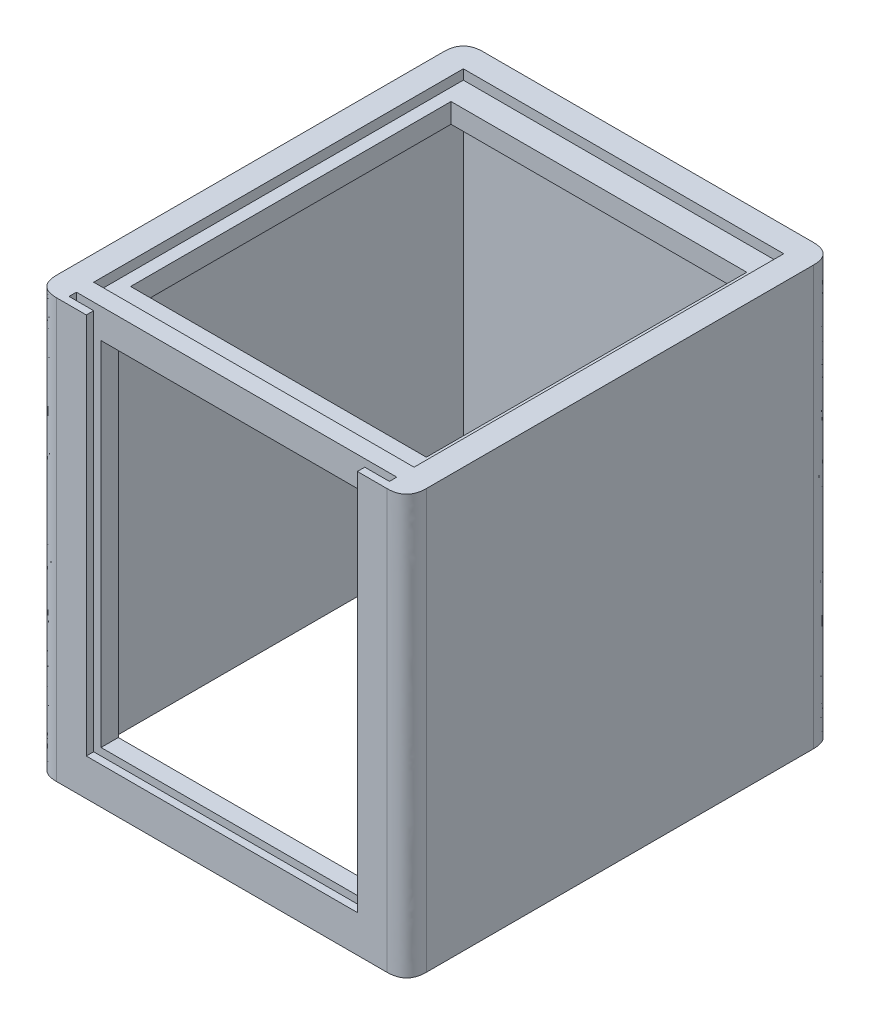
SolidWorks part; units mm, degrees
ref_plane "前基準面" through (0, 0, 0) normal (0, 0, 1) x (1, 0, 0)
ref_plane "上基準面" through (0, 0, 0) normal (0, 1, 0) x (1, 0, 0)
ref_plane "右基準面" through (0, 0, 0) normal (1, 0, 0) x (0, 0, -1)
sketch "草圖2" plane through (0, 0, 0) normal (0, 1, 0) x (1, 0, 0)
  line L1 (-75, -85) -> (75, -85)
  line L2 (-75, -85) -> (-75, 85)
  line L3 (-75, 85) -> (75, 85)
  line L4 (75, -85) -> (75, 85)
  line L5 (-75, -85) -> (75, 85) construction
  line L6 (-75, 85) -> (75, -85) construction
  point P0 (0, 0)
  dimension "D1" = 150
  dimension "D2" = 170
extrude "填料-伸長2" add sketch "草圖2" along normal blind 170
shell "薄殼5" thickness 4 removed face at (0, 0, 0) removed face at (0, 85, 85)
sketch "草圖3" plane through (0, 170, 0) normal (0, 1, 0) x (1, 0, 0)
  line L1 (-65, -75) -> (65, -75)
  line L2 (-65, -75) -> (-65, 75)
  line L3 (-65, 75) -> (65, 75)
  line L4 (65, -75) -> (65, 75)
  line L5 (-65, -75) -> (65, 75) construction
  line L6 (-65, 75) -> (65, -75) construction
  point P0 (0, 0)
  dimension "D1" = 150
  dimension "D2" = 130
extrude "除料-伸長1" cut sketch "草圖3" against normal through all
sketch "草圖4" plane through (0, 166, 0) normal (0, -1, 0) x (1, 0, 0)
  line L1 (60, -65) -> (-60, -65)
  line L2 (60, -65) -> (60, 65)
  line L3 (60, 65) -> (-60, 65)
  line L4 (-60, -65) -> (-60, 65)
  line L5 (60, -65) -> (-60, 65) construction
  line L6 (60, 65) -> (-60, -65) construction
  line L7 (75, -85) -> (-75, -85)
  line L8 (75, -85) -> (75, 85)
  line L9 (75, 85) -> (-75, 85)
  line L10 (-75, -85) -> (-75, 85)
  line L11 (75, -85) -> (-75, 85) construction
  line L12 (75, 85) -> (-75, -85) construction
  point P0 (0, 0)
  point P6 (0, 0)
  dimension "D1" = 120
  dimension "D2" = 130
extrude "填料-伸長3" add sketch "草圖4" along normal blind 8
sketch "草圖5" plane through (0, 0, 85) normal (0, 0, 1) x (1, 0, 0)
  line L0 (55, 170) -> (75, 170)
  line L1 (-75, 170) -> (-55, 170)
  line L2 (-75, 170) -> (-75, 0)
  line L3 (-75, 0) -> (75, 0)
  line L4 (75, 170) -> (75, 0)
  line L6 (-55, 170) -> (-55, 15)
  line L7 (-55, 15) -> (55, 15)
  line L8 (55, 170) -> (55, 15)
  dimension "D1" = 20
  dimension "D2" = 20
  dimension "D3" = 15
extrude "填料-伸長4" add sketch "草圖5" against normal up to surface (10 mm away) and the other way blind 3 up to face at (0, 168, 75)
sketch "草圖6" plane through (0, 170, 0) normal (0, 1, 0) x (1, 0, 0)
  line L0 (-55, -85) -> (55, -85) construction
  line L1 (-65, -85) -> (65, -85)
  line L2 (-65, -85) -> (-65, -82)
  line L3 (-65, -82) -> (65, -82)
  line L4 (65, -85) -> (65, -82)
  line L5 (0, -82) -> (0, 0) construction
  dimension "D1" = 130
  dimension "D2" = 3
extrude "除料-伸長2" cut sketch "草圖6" against normal blind 165
fillet "圓角1" radius 8 4 edges at (75, 85, -85) (-75, 85, -85) (75, 85, 88) (-75, 85, 88) conic rho 0.5
